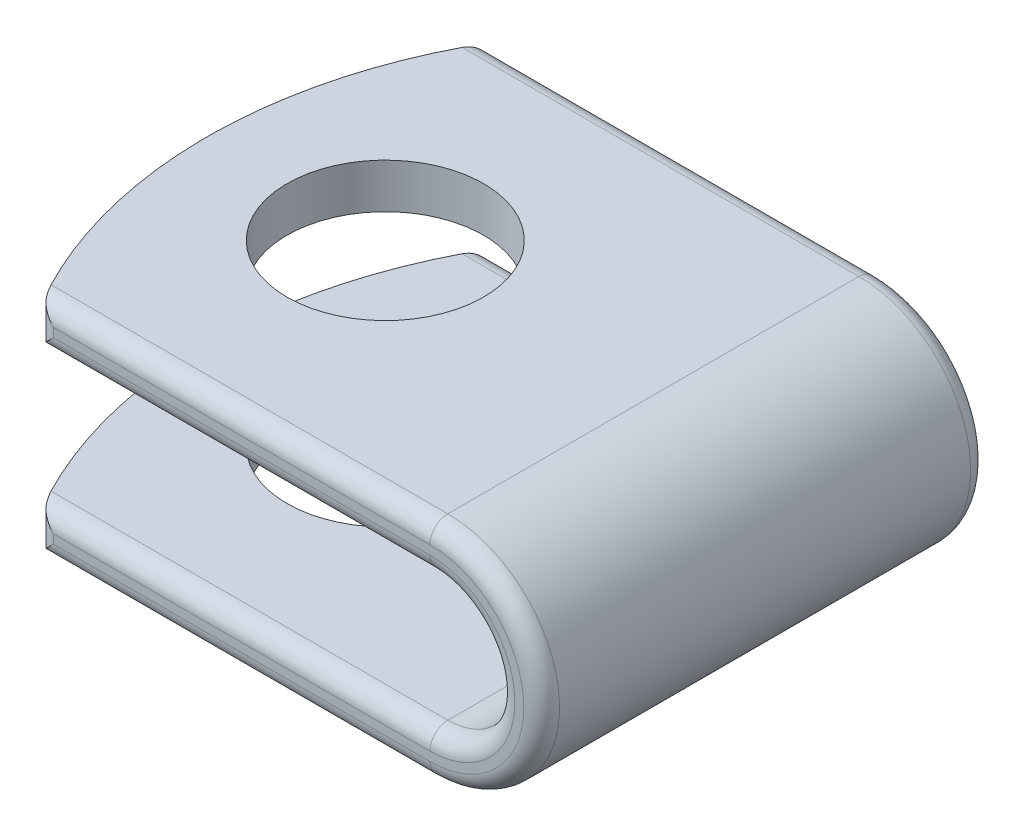
SolidWorks part; units mm, degrees
ref_plane "Alzado" through (0, 0, 0) normal (0, 0, 1) x (1, 0, 0)
ref_plane "Planta" through (0, 0, 0) normal (0, 1, 0) x (1, 0, 0)
ref_plane "Vista lateral" through (0, 0, 0) normal (1, 0, 0) x (0, 0, -1)
sketch "Croquis1" plane through (0, 0, 0) normal (0, 0, 1) x (1, 0, 0)
  line L0 (-5, 1.25) -> (0, 1.25)
  line L1 (-5, -1.25) -> (0, -1.25)
  line L2 (-5, -0.75) -> (0, -0.75)
  line L3 (-5, 0.75) -> (0, 0.75)
  line L4 (-5, -0.75) -> (-5, -1.25)
  line L5 (-5, 0.75) -> (-5, 1.25)
  arc A0 (0, 1.25) -> (0, -1.25) centre (0, 0) cw
  arc A1 (0, 0.75) -> (0, -0.75) centre (0, 0) cw
  point P5 (0, 0)
  point P6 (0, 0)
  point P12 (-0.0186, 0.9999)
  point P13 (0, 0)
  point P15 (0, 0)
  point P16 (0.5779, -0.8161)
  point P17 (0.8271, 1.2486)
  point P18 (0, 0)
  dimension "D1" = 5
  dimension "D2" = 2.5
  dimension "D3" = 0.5
extrude "Saliente-Extruir1" add sketch "Croquis1" along normal blind 2.5 and the other way blind 2.5
sketch "Croquis2" plane through (0, 1.25, 0) normal (0, 1, 0) x (1, 0, 0)
  line L1 (0, 2.5) -> (-5, 2.5) construction
  line L2 (0, -2.5) -> (-5, -2.5) construction
  line L3 (-5, 2.5) -> (-5, -2.5) construction
  arc A0 (-5, 0.0755) -> (-4.3308, 2.5) centre (0, 0) cw
  arc A1 (-5, 0.0755) -> (-4.3308, -2.5) centre (0, 0) ccw
  circle A2 centre (-3, 0) radius 1.1
  line M1 (-5, 2.5) -> (-5, -2.5)
  line M2 (-5, -2.5) -> (0, -2.5)
  line M4 (0, 2.5) -> (-5, 2.5)
  dimension "D1" = 2.2
  dimension "D2" = 3
extrude "Cortar-Extruir1" cut sketch "Croquis2" against normal through all contours A2 | A1 M1 M2 | A0 M1 M4 region at (-4.8017, 1.25, -1.8853) region at (-4.8017, 1.25, 1.8853) region at (-3, 1.25, 0)
fillet "Redondeo1" radius 0.2 8 edges at (-2.1654, -0.75, 2.5) (0.75, 0, 2.5) (-2.1654, 0.75, 2.5) (-4.3308, 1, 2.5) (-2.1654, 1.25, 2.5) (1.25, 0, 2.5) (-2.1654, -1.25, 2.5) (-4.3308, -1, 2.5)
fillet "Redondeo2" radius 0.2 8 edges at (-2.1654, 0.75, -2.5) (0.75, 0, -2.5) (-2.1654, -0.75, -2.5) (-4.3308, -1, -2.5) (-2.1654, -1.25, -2.5) (1.25, 0, -2.5) (-2.1654, 1.25, -2.5) (-4.3308, 1, -2.5)
